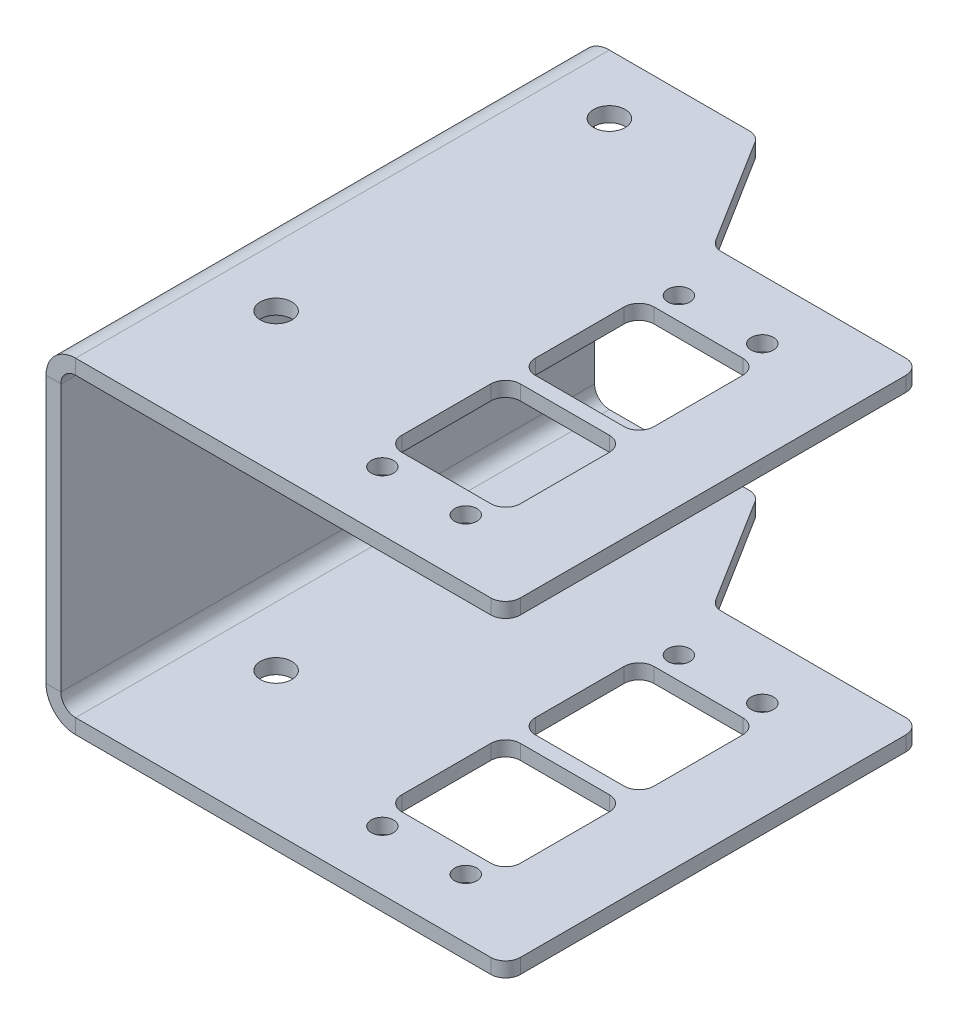
SolidWorks part; units mm, degrees
note: The reader was unsure of these and kept them because the rebuilt part matched: flange length of "Edge-Flange1".
material "5052-H32"
ref_plane "Front Plane" through (0, 0, 0) normal (0, 0, 1) x (1, 0, 0)
ref_plane "Top Plane" through (0, 0, 0) normal (0, 1, 0) x (1, 0, 0)
ref_plane "Right Plane" through (0, 0, 0) normal (1, 0, 0) x (0, 0, -1)
sketch "Sketch1" plane through (0, 0, 0) normal (1, 0, 0) x (0, 0, -1)
  line L1 (0, 0) -> (114.3, 0)
  line L2 (0, 0) -> (0, 69.85)
  line L3 (0, 69.85) -> (114.3, 69.85)
  line L4 (114.3, 0) -> (114.3, 69.85)
  dimension "D1" = 69.85
  dimension "D2" = 114.3
base flange "Base-Flange1" sketch "Sketch1" thickness 3.175 reverse thickness direction no parameters "D1"=3.175
edge flange "Edge-Flange1" sketch "Sketch10" flange profiles "Sketch10", "Sketch11" flange angle 90 flange length 98.425 flange position material inside bend radius 3.175 thickness 3.175 relief rectangular parameters "D6"=10, "D8"=1
sketch "Sketch10" plane through (0, 69.85, 0) normal (0, 1, 0) x (0, 0, 1)
  line L0 (-114.3, 0) -> (0, 0) construction
  line L1 (-114.3, 0) -> (0, 0)
  line L2 (-114.3, 0) -> (-114.3, 95.25)
  line L3 (-114.3, 95.25) -> (0, 95.25)
  line L4 (0, 95.25) -> (0, 0)
sketch "Sketch11" plane through (0, 0, 0) normal (0, -1, 0) x (0, 0, -1)
  line L0 (0, 0) -> (114.3, 0) construction
  line L1 (0, 0) -> (114.3, 0)
  line L2 (0, 0) -> (0, 95.25)
  line L3 (0, 95.25) -> (114.3, 95.25)
  line L4 (114.3, 95.25) -> (114.3, 0)
bend "EdgeBend1" bend radius 3.175 bend angle 90 parameters "D5"=1
bend "EdgeBend2" bend radius 3.175 bend angle 90 parameters "D5"=2
sketch "Sketch12" plane through (0, 69.85, 0) normal (0, 1, 0) x (1, 0, 0)
  line L0 (34.925, 114.3) -> (50.8, 88.9)
  line L1 (95.25, 114.3) -> (3.175, 114.3) construction
  line L2 (50.8, 88.9) -> (95.25, 88.9)
  line L3 (95.25, 0) -> (95.25, 114.3) construction
  line L4 (95.25, 88.9) -> (95.25, 114.3)
  line L5 (95.25, 114.3) -> (34.925, 114.3)
  line L6 (3.175, 0) -> (3.175, 114.3) construction
  line L7 (3.175, 0) -> (95.25, 0) construction
  line L9 (55.5625, 71.4375) -> (74.6125, 71.4375)
  line L10 (52.3875, 68.2625) -> (52.3875, 49.2125)
  line L11 (55.5625, 46.0375) -> (74.6125, 46.0375)
  line L12 (77.7875, 68.2625) -> (77.7875, 49.2125)
  line L13 (74.6125, 42.8625) -> (55.5625, 42.8625)
  line L14 (77.7875, 39.6875) -> (77.7875, 20.6375)
  line L15 (74.6125, 17.4625) -> (55.5625, 17.4625)
  line L16 (52.3875, 39.6875) -> (52.3875, 20.6375)
  circle A0 centre (56.1594, 76.2) radius 2.3812
  circle A1 centre (74.0181, 76.2) radius 2.3813
  circle A2 centre (56.1594, 12.7) radius 2.3812
  circle A3 centre (74.0181, 12.7) radius 2.3813
  arc A4 (52.3875, 49.2125) -> (55.5625, 46.0375) centre (55.5625, 49.2125) ccw
  arc A5 (55.5625, 42.8625) -> (52.3875, 39.6875) centre (55.5625, 39.6875) ccw
  arc A6 (55.5625, 17.4625) -> (52.3875, 20.6375) centre (55.5625, 20.6375) cw
  arc A7 (77.7875, 20.6375) -> (74.6125, 17.4625) centre (74.6125, 20.6375) cw
  arc A8 (74.6125, 42.8625) -> (77.7875, 39.6875) centre (74.6125, 39.6875) cw
  arc A9 (74.6125, 46.0375) -> (77.7875, 49.2125) centre (74.6125, 49.2125) ccw
  arc A10 (74.6125, 71.4375) -> (77.7875, 68.2625) centre (74.6125, 68.2625) cw
  arc A11 (55.5625, 71.4375) -> (52.3875, 68.2625) centre (55.5625, 68.2625) ccw
  circle A12 centre (15.875, 101.6) radius 3.3734
  circle A13 centre (15.875, 30.226) radius 3.3734
  dimension "D11" = 4.7625
  dimension "D16" = 3.175
  dimension "D20" = 6.7469
  dimension "D1" = 44.45
  dimension "D2" = 31.75
  dimension "D3" = 88.9
  dimension "D4" = 25.4
  dimension "D5" = 25.4
  dimension "D6" = 25.4
  dimension "D7" = 25.4
  dimension "D8" = 3.175
  dimension "D9" = 17.4625
  dimension "D10" = 17.4625
  dimension "D12" = 17.8587
  dimension "D13" = 12.7
  dimension "D14" = 12.7
  dimension "D15" = 21.2319
  dimension "D17" = 30.226
  dimension "D18" = 12.7
  dimension "D19" = 12.7
extrude "Cut-Extrude1" cut sketch "Sketch12" against normal through all normal cut yes
fillet "Fillet1" radius 3.175 8 edges at (95.25, 1.5875, 0) (95.25, 68.2625, 0) (95.25, 68.2625, -88.9) (95.25, 1.5875, -88.9) (34.925, 1.5875, -114.3) (50.8, 1.5875, -88.9) (50.8, 68.2625, -88.9) (34.925, 68.2625, -114.3)
sketch "Bend-Lines1" [suppressed] plane through (0, 0, 0) normal (0, 1, 0) x (1, 0, 0)
sketch "Bounding-Box1" [suppressed] plane through (0, 0, 0) normal (0, 1, 0) x (1, 0, 0)
sheet metal parameters "Sheet-Metal1" thickness 3.175 parameters "D1"=3.175
flat pattern "Flat-Pattern1" [suppressed]
sketch "Bend-Lines2" plane through (0, 0, 0) normal (0, 1, 0) x (1, 0, 0)
sketch3d "Bounding-Box2" [suppressed]
  line L0 (-114.3, 0, 0) -> (0, 0, 0) construction
  line L1 (-114.3, 69.85, 0) -> (0, 69.85, 0) construction
  line L2 (-114.3, 0, 0) -> (-114.3, 69.85, 0) construction
  line L3 (0, 0, 0) -> (0, 69.85, 0) construction
sheet metal parameters "Sheet-Metal2" thickness 3.175 parameters "D1"=3.175
flat pattern "Flat-Pattern1"
sketch "Bend-Lines2" plane through (0, 0, 0) normal (1, 0, 0) x (0, 0, -1)
  line L0 (0, 2.6095) -> (114.3, 2.6095) construction
  line L1 (114.3, 67.2405) -> (0, 67.2405) construction
  line L2 (0, 2.6095) -> (114.3, 2.6095) construction
  line L3 (114.3, 67.2405) -> (0, 67.2405) construction
sketch3d "Bounding-Box2" [suppressed]
  line L0 (0, 153.5309, 0) -> (0, -83.6809, 0) construction
  line L1 (114.3, 153.5309, 0) -> (114.3, -83.6809, 0) construction
  line L2 (0, 153.5309, 0) -> (114.3, 153.5309, 0) construction
  line L3 (0, -83.6809, 0) -> (114.3, -83.6809, 0) construction
bend of the flat pattern "Flatten-<EdgeBend1>1"
bend of the flat pattern "Flatten-<EdgeBend2>1"
sheet metal parameters "Sheet-Metal3" thickness 3.175 parameters "D1"=3.175
flat pattern "Flat-Pattern1"
sketch "Bend-Lines2" plane through (0, 0, 0) normal (1, 0, 0) x (0, 0, -1)
  line L0 (0, 2.6095) -> (114.3, 2.6095) construction
  line L1 (114.3, 67.2405) -> (0, 67.2405) construction
  line L2 (0, 2.6095) -> (114.3, 2.6095) construction
  line L3 (114.3, 67.2405) -> (0, 67.2405) construction
sketch3d "Bounding-Box2" [suppressed]
  line L0 (0, 163.0559, 0) -> (0, -93.2059, 0) construction
  line L1 (114.3, 163.0559, 0) -> (114.3, -93.2059, 0) construction
  line L2 (0, 163.0559, 0) -> (114.3, 163.0559, 0) construction
  line L3 (0, -93.2059, 0) -> (114.3, -93.2059, 0) construction
bend of the flat pattern "Flatten-<EdgeBend1>1"
bend of the flat pattern "Flatten-<EdgeBend2>1"
